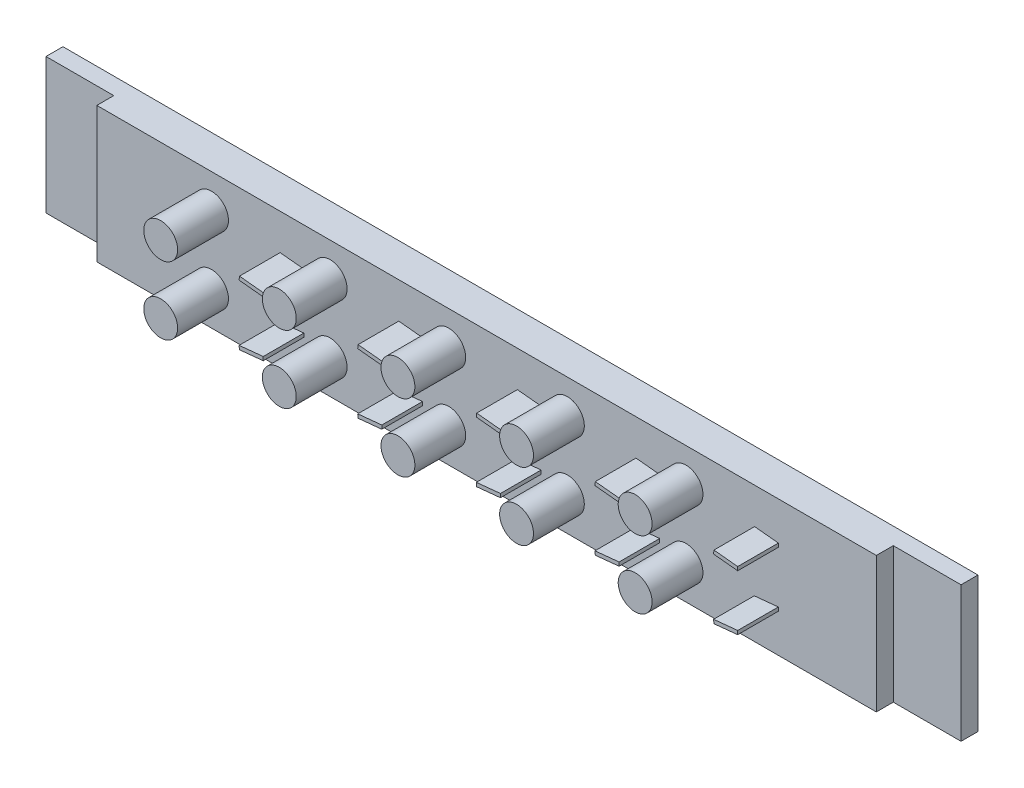
SolidWorks part; units mm, degrees
ref_plane "前视基准面" through (0, 0, 0) normal (0, 0, 1) x (1, 0, 0)
ref_plane "上视基准面" through (0, 0, 0) normal (0, 1, 0) x (1, 0, 0)
ref_plane "右视基准面" through (0, 0, 0) normal (1, 0, 0) x (0, 0, -1)
sketch "草图1" plane through (0, 0, 0) normal (0, 0, 1) x (1, 0, 0)
  line L0 (-192.4036, 24.089) -> (-192.4036, -55.911)
  line L1 (307.5964, 24.089) -> (-232.4036, 24.089)
  line L2 (307.5964, -55.911) -> (-232.4036, -55.911)
  line L3 (-192.4036, 24.089) -> (-192.4036, -55.911)
  line L4 (267.5964, -55.911) -> (267.5964, 24.089)
  line L5 (-232.4036, 24.089) -> (-232.4036, -55.911)
  line L6 (307.5964, 24.089) -> (307.5964, -55.911)
  circle A0 centre (-124.7232, 4.089) radius 10
  circle A1 centre (-54.7232, 4.089) radius 10
  circle A2 centre (15.2768, 4.089) radius 10
  circle A3 centre (85.2768, 4.089) radius 10
  circle A4 centre (155.2768, 4.089) radius 10
  circle A5 centre (-124.7232, -35.911) radius 10
  circle A6 centre (-54.7232, -35.911) radius 10
  circle A7 centre (15.2768, -35.911) radius 10
  circle A8 centre (85.2768, -35.911) radius 10
  circle A9 centre (155.2768, -35.911) radius 10
extrude "凸台-拉伸1" add sketch "草图1" against normal blind 10 contours L1 L5 L2 L0 | L2 L4 L1 L0 A9 A8 A7 A6 A5 A4 A3 A2 A1 A0 | L6 L1 L4 L2 region at (39.6797, -15.911, 0) region at (-212.4036, -15.911, 0) region at (287.5964, -15.911, 0)
extrude "凸台-拉伸2" add sketch "草图1<3>" along normal blind 10 contours L2 L4 L1 L0 A9 A8 A7 A6 A5 A4 A3 A2 A1 A0 region at (39.6797, -15.911, 0)
sketch "草图1<3>" plane through (0, 0, 0) normal (0, 0, 1) x (1, 0, 0) same geometry as "草图1"
extrude "凸台-拉伸3" add sketch "草图1<4>" along normal blind 50 from vertex contours A5 | A0 | A6 | A7 | A3 | A4 | A1 | A2 | A8 | A9 region at (-124.7232, 4.089, 0) region at (85.2768, 4.089, 0) region at (155.2768, 4.089, 0) region at (-124.7232, -35.911, 0) region at (-54.7232, -35.911, 0) region at (15.2768, -35.911, 0) starting at point (-232.4036, 24.089, -10)
sketch "草图1<4>" plane through (0, 0, 0) normal (0, 0, 1) x (1, 0, 0) same geometry as "草图1"
sketch "草图2" plane through (0, 0, 10) normal (0, 0, 1) x (1, 0, 0)
  line L0 (-70.2143, 1.5126) -> (-84.2386, 2.9155)
  line L1 (-79.8953, 2.481) -> (-70.2143, 1.5126) construction
  line L2 (-84.2386, 2.9155) -> (-84.4546, 0.7567)
  line L3 (-84.4546, 0.7567) -> (-70.2143, -0.6678)
  line L4 (-70.2143, -0.6678) -> (-70.2143, 1.5126)
  line L5 (-232.4036, -15.911) -> (267.5964, -15.911) construction
  line L9 (-232.4036, 24.089) -> (-232.4036, -55.911) construction
  line L10 (267.5964, -55.911) -> (267.5964, 24.089) construction
  line L11 (-70.2143, -31.1543) -> (-70.2143, -33.3347)
  line L12 (-84.4546, -32.5788) -> (-70.2143, -31.1543)
  line L13 (-84.2386, -34.7375) -> (-84.4546, -32.5788)
  line L14 (-70.2143, -33.3347) -> (-84.2386, -34.7375)
  dimension "D1" = 14.0943
  dimension "D2" = 2.1696
  dimension "D3" = 14.3113
  dimension "D4" = 2.1804
  dimension "D5" = 500
extrude "凸台-拉伸4" add sketch "草图2" along normal blind 24
pattern_linear "阵列(线性)2" count 5 spacing 70 along (1, 0, 0) of "凸台-拉伸4"
